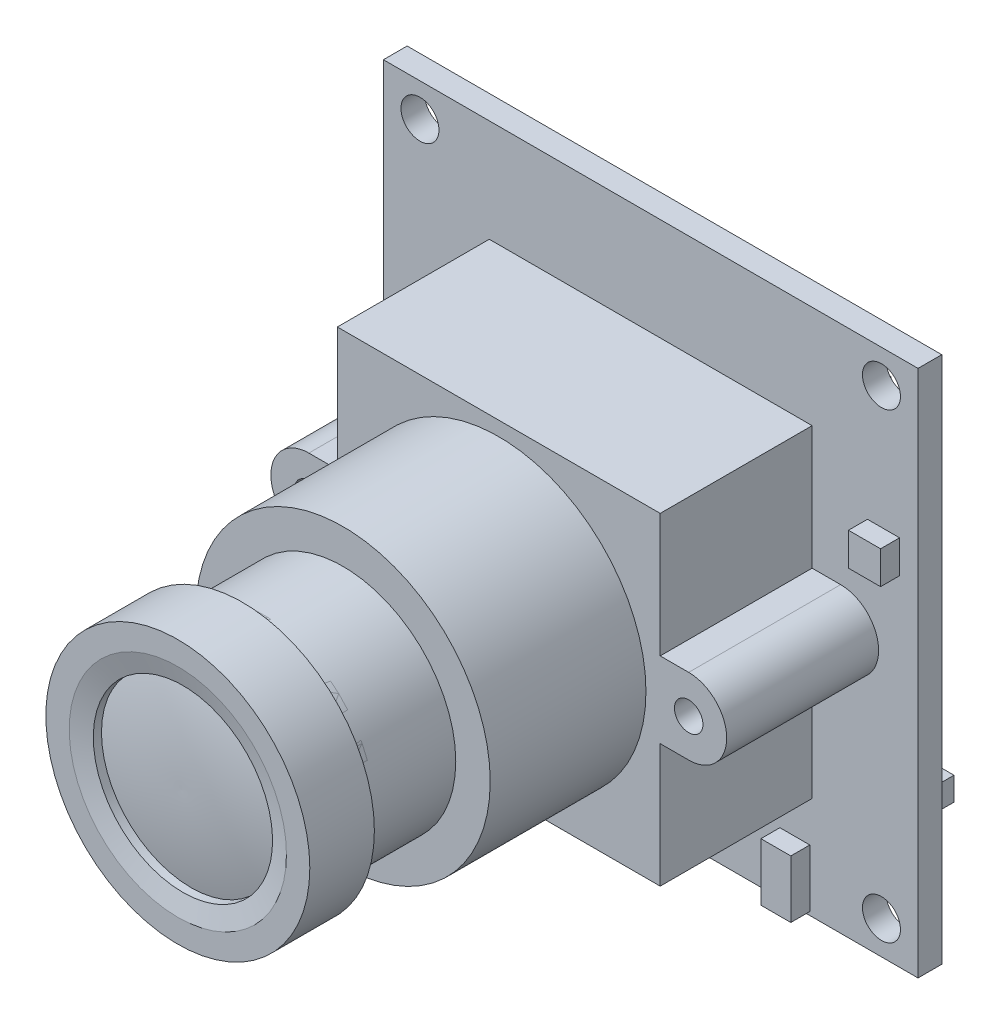
SolidWorks part; units mm, degrees
ref_plane "Front Plane" through (0, 0, 0) normal (0, 0, 1) x (1, 0, 0)
ref_plane "Top Plane" through (0, 0, 0) normal (0, 1, 0) x (1, 0, 0)
ref_plane "Right Plane" through (0, 0, 0) normal (1, 0, 0) x (0, 0, -1)
sketch "Sketch1" plane through (0, 0, 0) normal (0, 0, 1) x (1, 0, 0)
  line L1 (-14.075, 13.9) -> (14.075, 13.9)
  line L2 (-14.075, 13.9) -> (-14.075, -13.9)
  line L3 (-14.075, -13.9) -> (14.075, -13.9)
  line L4 (14.075, 13.9) -> (14.075, -13.9)
  line L5 (-14.075, 13.9) -> (14.075, -13.9) construction
  line L6 (-14.075, -13.9) -> (14.075, 13.9) construction
  point P0 (0, 0)
  dimension "D1" = 27.8
  dimension "D2" = 28.15
extrude "Base shape" add sketch "Sketch1" along normal blind 1.25
sketch "Sketch2" plane through (0, 0, 1.25) normal (0, 0, 1) x (1, 0, 0)
  line L0 (-14.075, 0) -> (14.075, 0) construction
  line L1 (-14.075, 13.9) -> (-14.075, -13.9) construction
  line L2 (14.075, -13.9) -> (14.075, 13.9) construction
  line L3 (0, 13.9) -> (0, -13.9) construction
  line L4 (14.075, 13.9) -> (-14.075, 13.9) construction
  line L5 (-14.075, -13.9) -> (14.075, -13.9) construction
  line L6 (12.15, 12.15) -> (-12.15, 12.15) construction
  line L7 (12.15, 12.15) -> (12.15, -12.15) construction
  circle A0 centre (12.15, 12.15) radius 1
  circle A1 centre (-12.15, 12.15) radius 1
  circle A2 centre (12.15, -12.15) radius 1
  circle A3 centre (-12.15, -12.15) radius 1
  point P14 (0, 12.15)
  point P16 (12.15, 0)
  dimension "D1" = 24.3
  dimension "D2" = 2
extrude "Mounting holes" cut sketch "Sketch2" against normal up to next
sketch "Sketch3" plane through (0, 0, 1.25) normal (0, 0, 1) x (1, 0, 0)
  line L0 (0, 13.9) -> (0, -13.9) construction
  line L1 (14.075, 13.9) -> (-14.075, 13.9) construction
  line L2 (-14.075, -13.9) -> (14.075, -13.9) construction
  line L3 (-14.075, 0) -> (14.075, 0) construction
  line L4 (-14.075, 13.9) -> (-14.075, -13.9) construction
  line L5 (14.075, -13.9) -> (14.075, 13.9) construction
  line L6 (-10, 0) -> (10, 0) construction
  line L7 (-8.5, 8.5) -> (8.5, 8.5)
  line L8 (-8.5, 8.5) -> (-8.5, -8.5)
  line L9 (-8.5, -8.5) -> (8.5, -8.5)
  line L10 (8.5, 8.5) -> (8.5, -8.5)
  line L11 (-8.5, 8.5) -> (8.5, -8.5) construction
  line L12 (-8.5, -8.5) -> (8.5, 8.5) construction
  line L13 (-12, 0) -> (12, 0) construction
  line L14 (-10, -2) -> (10, -2) construction
  line L15 (-10, 2) -> (-8.5, 2)
  line L16 (-10, -2) -> (-8.5, -2)
  line L17 (10, 2) -> (8.5, 2)
  line L18 (10, -2) -> (8.5, -2)
  circle A0 centre (-10, 0) radius 2
  circle A1 centre (10, 0) radius 2
  circle A2 centre (-10, 0) radius 0.75
  circle A3 centre (10, 0) radius 0.75
  point P12 (0, 0)
  point P23 (0, -2)
  dimension "D4" = 1.5
  dimension "D1" = 17
  dimension "D2" = 24
  dimension "D3" = 20
extrude "Cam base" add sketch "Sketch3" along normal blind 8 contours L8 A0 A2 | A1 L10 L7 L8 A0 L9 | A1 L10 A3 | A1 L10 L18 | L10 A1 | A1 L17 L10 | L8 A0 | A0 L8 L15 | A0 L16 L8 region at (0, 0, 1.25) region at (-8.8611, 1.8045, 1.25) region at (8.8611, 1.8045, 1.25) region at (-8.2977, 0, 1.25) region at (-8.5532, 0, 1.25) region at (9.199, 1.7744, 1.25) region at (8.2977, 0, 1.25) region at (-8.8611, -1.8045, 1.25) region at (8.8611, -1.8045, 1.25)
sketch "Sketch4" plane through (0, 0, 9.25) normal (0, 0, 1) x (1, 0, 0)
  circle A0 centre (0, 0) radius 7.75
  dimension "D1" = 15.5
extrude "Cam step 1" add sketch "Sketch4" along normal blind 8.2
sketch "Sketch5" plane through (0, 0, 17.45) normal (0, 0, 1) x (1, 0, 0)
  circle A0 centre (0, 0) radius 5.935
  dimension "D1" = 11.87
extrude "Cam step 2" add sketch "Sketch5" along normal blind 5.3
sketch "Sketch6" plane through (0, 0, 22.75) normal (0, 0, 1) x (1, 0, 0)
  circle A0 centre (0, 0) radius 6.95
  dimension "D1" = 13.9
extrude "Cam step 3" add sketch "Sketch6" along normal offset from surface (3.4 mm away) 24.9 up to face at (0, 0, 1.25) offset beyond the face yes
ref_axis "Lens axis" through (0, 0, 26.15) along (0, 0, -1)
sketch "Sketch7" plane through (0, 0, 0) normal (1, 0, 0) x (0, 0, -1)
  line L0 (-26.15, 0) -> (-9.25, 0) construction
  line L1 (-26.15, 6.95) -> (-26.15, -6.95) construction
  line L2 (-9.25, 2) -> (-9.25, -2) construction
  line L3 (-26.15, 4.72) -> (-9.25, 4.72) construction
  line L4 (-9.25, 7.75) -> (-9.25, -7.75) construction
  line L5 (-22.75, 6.95) -> (-26.15, 6.95) construction
  line L6 (-25.95, 4.72) -> (-25.95, 0) construction
  line L7 (-25.45, 0) -> (-25.45, 4.72) construction
  line L8 (-25.45, 2.36) -> (-25.95, 2.36) construction
  line L9 (-25.85, 4.72) -> (-25.85, 0) construction
  line L10 (-25.45, 4.72) -> (-26.15, 4.72)
  line L11 (-26.15, 4.72) -> (-26.15, 0)
  line L12 (-26.15, 0) -> (-25.95, 0)
  spline S0 degree 2 poles (-25.95, 0) (-25.9967, 2.3913) (-25.45, 4.72) knots 0 0 0 1 1 1
  dimension "D1" = 2.23
  dimension "D2" = 0.2
  dimension "D3" = 0.5
  dimension "D4" = 0.1
revolve "Lens profile" cut sketch "Sketch7" angle 360 about L0
chamfer "Lens chamfer" distance 1 angle 15 1 edges at (0, -4.72, 26.15) first distance on face at (0, -4.72, 26.15)
sketch "Sketch8" plane through (0, 0, 22.75) normal (0, 0, -1) x (-1, 0, 0)
  circle A0 centre (0, 0) radius 5.935 construction
  circle A1 centre (0, 0) radius 5.935
extrude "Lens background" add sketch "Sketch8" along normal blind 1 separate body
sketch "Sketch9" plane through (0, 0, 1.25) normal (0, 0, 1) x (1, 0, 0)
  line L1 (-13.2957, -8.4155) -> (-10.4905, -8.4155)
  line L2 (-13.2957, -8.4155) -> (-13.2957, -4.2269)
  line L3 (-13.2957, -4.2269) -> (-10.4905, -4.2269)
  line L4 (-10.4905, -8.4155) -> (-10.4905, -4.2269)
  line L9 (6.8015, -10.6826) -> (8.377, -10.6826)
  line L10 (6.8015, -10.6826) -> (6.8015, -13.7184)
  line L11 (6.8015, -13.7184) -> (8.377, -13.7184)
  line L12 (8.377, -10.6826) -> (8.377, -13.7184)
  line L13 (11.4128, 5.6872) -> (13.1035, 5.6872)
  line L14 (11.4128, 5.6872) -> (11.4128, 3.958)
  line L15 (11.4128, 3.958) -> (13.1035, 3.958)
  line L16 (13.1035, 5.6872) -> (13.1035, 3.958)
extrude "Front components" add sketch "Sketch9" along normal blind 1
sketch "Sketch10" plane through (0, 0, 0) normal (0, 0, -1) x (-1, 0, 0)
  line L1 (-9.9141, 5.3029) -> (-4.8033, 5.3029)
  line L2 (-9.9141, 5.3029) -> (-9.9141, 10.0678)
  line L3 (-9.9141, 10.0678) -> (-4.8033, 10.0678)
  line L4 (-4.8033, 5.3029) -> (-4.8033, 10.0678)
  line L5 (-7.5701, 2.1135) -> (-5.9946, 2.1135)
  line L6 (-7.5701, 2.1135) -> (-7.5701, 0.6533)
  line L7 (-7.5701, 0.6533) -> (-5.9946, 0.6533)
  line L8 (-5.9946, 2.1135) -> (-5.9946, 0.6533)
  line L9 (-13.2188, -6.4557) -> (-11.528, -6.4557)
  line L10 (-13.2188, -6.4557) -> (-13.2188, -7.6854)
  line L11 (-13.2188, -7.6854) -> (-11.528, -7.6854)
  line L12 (-11.528, -6.4557) -> (-11.528, -7.6854)
  line L13 (-8.9919, -9.3761) -> (-7.5316, -9.3761)
  line L14 (-8.9919, -9.3761) -> (-8.9919, -12.1044)
  line L15 (-8.9919, -12.1044) -> (-7.5316, -12.1044)
  line L16 (-7.5316, -9.3761) -> (-7.5316, -12.1044)
  line L17 (-4.7265, -4.6496) -> (-3.3047, -4.6496)
  line L18 (-4.7265, -4.6496) -> (-4.7265, -5.9177)
  line L19 (-4.7265, -5.9177) -> (-3.3047, -5.9177)
  line L20 (-3.3047, -4.6496) -> (-3.3047, -5.9177)
  line L21 (-0.0384, -5.6103) -> (1.4986, -5.6103)
  line L22 (-0.0384, -5.6103) -> (-0.0384, -8.4539)
  line L23 (-0.0384, -8.4539) -> (1.4986, -8.4539)
  line L24 (1.4986, -5.6103) -> (1.4986, -8.4539)
  line L25 (10.3752, -3.958) -> (13.1804, -3.958)
  line L26 (10.3752, -3.958) -> (10.3752, -5.6487)
  line L27 (10.3752, -5.6487) -> (13.1804, -5.6487)
  line L28 (13.1804, -3.958) -> (13.1804, -5.6487)
  line L29 (10.9132, 3.4584) -> (13.6415, 3.4584)
  line L30 (10.9132, 3.4584) -> (10.9132, 2.1519)
  line L31 (10.9132, 2.1519) -> (13.6415, 2.1519)
  line L32 (13.6415, 3.4584) -> (13.6415, 2.1519)
  line L33 (7.6854, -8.9919) -> (9.2224, -8.9919)
  line L34 (7.6854, -8.9919) -> (7.6854, -10.4137)
  line L35 (7.6854, -10.4137) -> (9.2224, -10.4137)
  line L36 (9.2224, -8.9919) -> (9.2224, -10.4137)
  line L37 (-0.7301, 2.4593) -> (6.2636, 2.4593)
  line L38 (-0.7301, 2.4593) -> (-0.7301, 9.184)
  line L39 (-0.7301, 9.184) -> (6.2636, 9.184)
  line L40 (6.2636, 2.4593) -> (6.2636, 9.184)
  circle A0 centre (-8.5692, -6.6478) radius 1.7206
  circle A1 centre (-4.2269, -8.377) radius 1.6986
extrude "Rear components" add sketch "Sketch10" along normal blind 1.5
sketch "Sketch11" plane through (0, 0, 0) normal (0, 0, -1) x (-1, 0, 0)
  line L0 (14.075, -13.9) -> (-14.075, -13.9) construction
  line L1 (0.475, -10.6) -> (10.475, -10.6)
  line L2 (0.475, -10.6) -> (0.475, -13.9)
  line L3 (0.475, -13.9) -> (10.475, -13.9)
  line L4 (10.475, -10.6) -> (10.475, -13.9)
  line L5 (14.075, 13.9) -> (14.075, -13.9) construction
  dimension "D1" = 10
  dimension "D2" = 3.3
  dimension "D3" = 3.6
extrude "Boss-Extrude9" add sketch "Sketch11" along normal blind 4.8 separate body
sketch "Sketch12" plane through (0, 0, -4.8) normal (0, 0, -1) x (-1, 0, 0)
  line L0 (0.475, -10.6) -> (0.475, -13.9) construction
  line L1 (0.875, -11) -> (4.125, -11)
  line L2 (0.875, -11) -> (0.875, -13.5)
  line L3 (0.875, -13.5) -> (4.125, -13.5)
  line L4 (4.125, -11) -> (4.125, -13.5)
  line L5 (5.375, -11) -> (10.075, -11)
  line L6 (5.375, -11) -> (5.375, -13.5)
  line L7 (5.375, -13.5) -> (10.075, -13.5)
  line L8 (10.075, -11) -> (10.075, -13.5)
  line L9 (0.875, -12.25) -> (0.475, -12.25) construction
  line L10 (2.5, -11) -> (2.5, -10.6) construction
  line L11 (10.075, -12.25) -> (10.475, -12.25) construction
  line L12 (10.475, -13.9) -> (10.475, -10.6) construction
  line L13 (10.475, -10.6) -> (0.475, -10.6) construction
  dimension "D1" = 0.4
  dimension "D2" = 1.25
  dimension "D3" = 4.7
extrude "Cut-Extrude2" cut sketch "Sketch12" against normal offset from surface (4.4 mm away) 0.4 up to face at (-8.4539, -9.7028, 0)
sketch "Sketch13" plane through (0, -10.6, 0) normal (0, 1, 0) x (1, 0, 0)
  line L0 (-10.475, 4.8) -> (-0.475, 4.8) construction
  line L1 (-0.875, 4.8) -> (-4.125, 4.8)
  line L2 (-0.875, 4.8) -> (-0.875, 3.2)
  line L3 (-0.875, 3.2) -> (-4.125, 3.2)
  line L4 (-4.125, 4.8) -> (-4.125, 3.2)
  line L6 (-5.375, 4.8) -> (-10.075, 4.8)
  line L7 (-5.375, 4.8) -> (-5.375, 3.2)
  line L8 (-5.375, 3.2) -> (-10.075, 3.2)
  line L9 (-10.075, 4.8) -> (-10.075, 3.2)
  dimension "D1" = 1.6
extrude "Cut-Extrude3" cut sketch "Sketch13" against normal up to next (0.4 mm away)
